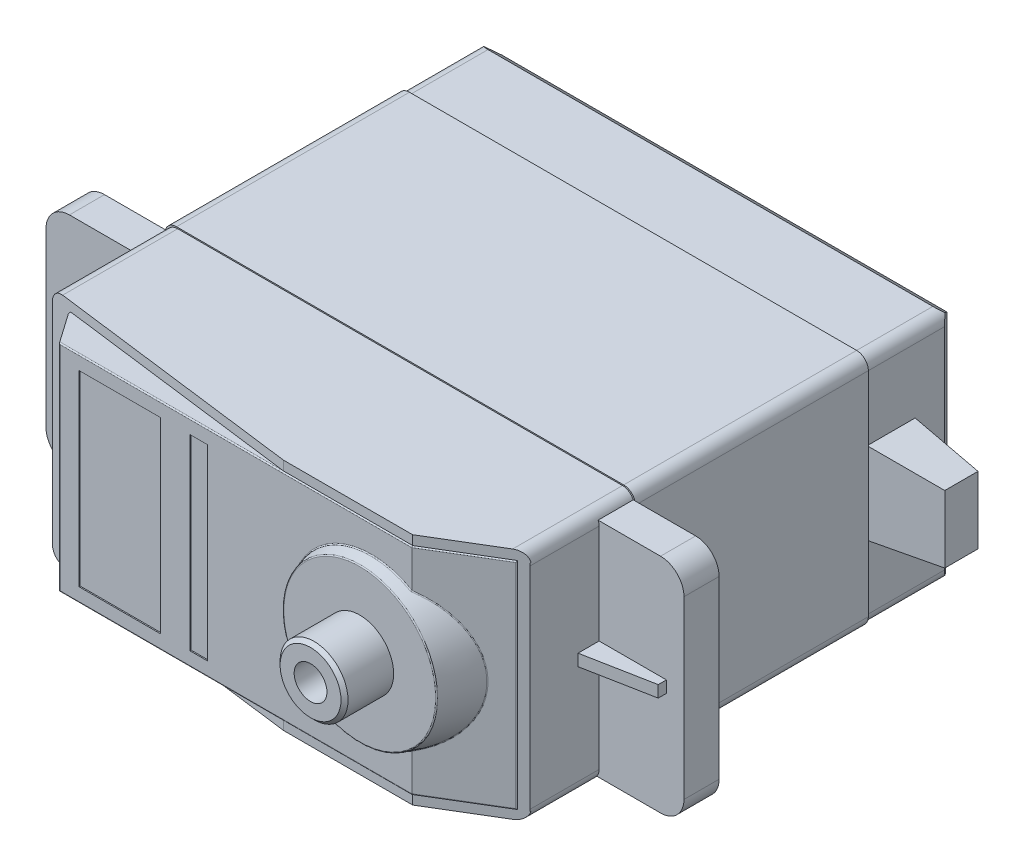
SolidWorks part; units mm, degrees
ref_plane "正面" through (0, 0, 0) normal (0, 0, 1) x (1, 0, 0)
ref_plane "平面" through (0, 0, 0) normal (0, 1, 0) x (1, 0, 0)
ref_plane "右側面" through (0, 0, 0) normal (1, 0, 0) x (0, 0, -1)
sketch "ｽｹｯﾁ1" plane through (0, 0, 0) normal (0, 0, 1) x (1, 0, 0)
  line L1 (20, -10) -> (-20, -10)
  line L2 (20, -10) -> (20, 10)
  line L3 (20, 10) -> (-20, 10)
  line L4 (-20, -10) -> (-20, 10)
  line L5 (20, -10) -> (-20, 10) construction
  line L6 (20, 10) -> (-20, -10) construction
  point P0 (0, 0)
  dimension "D1" = 40
  dimension "D2" = 20
extrude "ﾎﾞｽ - 押し出し1" add sketch "ｽｹｯﾁ1" along normal blind 40.4
chamfer "面取り1" distance 1 angle 50 4 edges at (0, -10, 0) (20, 0, 0) (0, 10, 0) (-20, 0, 0) first distance on face at (0, 0, 0)
ref_plane "平面1" through (0, 0, 27.7) normal (0, 0, -1) x (-1, 0, 0)
sketch "ｽｹｯﾁ3" plane through (0, 0, 27.7) normal (0, 0, -1) x (-1, 0, 0)
  line L0 (-20, -10) -> (-20, 10) construction
  line L1 (-20, -9.6) -> (-27.25, -9.6)
  line L2 (-20, -9.6) -> (-20, 9.4)
  line L3 (-20, 9.4) -> (-27.25, 9.4)
  line L4 (-27.25, -9.6) -> (-27.25, 9.4)
  line L5 (20, 10) -> (20, -10) construction
  line L6 (20, -9.3258) -> (27.25, -9.3258)
  line L7 (20, -9.3258) -> (20, 9.4)
  line L8 (20, 9.4) -> (27.25, 9.4)
  line L9 (27.25, -9.3258) -> (27.25, 9.4)
  line L10 (-20, 10) -> (20, 10) construction
  dimension "D1" = 0.6
  dimension "D2" = 19
  dimension "D3" = 54.5
extrude "ﾎﾞｽ - 押し出し2" add sketch "ｽｹｯﾁ3" against normal blind 3
sketch "ｽｹｯﾁ4" plane through (0, 0, 0) normal (0, 1, 0) x (1, 0, 0)
  line L0 (-25.75, -30.7) -> (-25.75, -31.4)
  line L1 (-27.25, -30.7) -> (-20, -30.7) construction
  line L2 (-25.75, -31.4) -> (-20, -32.5)
  line L3 (-20, -40.4) -> (-20, -1.1918) construction
  line L4 (-20, -32.5) -> (-20, -30.7)
  line L5 (-20, -30.7) -> (-25.75, -30.7)
  line L6 (-27.25, -30.7) -> (-27.25, -27.7) construction
  dimension "D1" = 1.8
  dimension "D2" = 0.7
  dimension "D3" = 1.5
extrude "ﾎﾞｽ - 押し出し3" add sketch "ｽｹｯﾁ4" along normal mid plane 1
mirror "ﾐﾗｰ1" about plane through (0, 0, 0) normal (1, 0, 0) of "ﾎﾞｽ - 押し出し3"
fillet "ﾌｨﾚｯﾄ1" radius 1 4 edges at (20, -10, 20.7959) (20, 10, 20.7959) (-20, 10, 20.7959) (-20, -10, 20.7959)
fillet "ﾌｨﾚｯﾄ2" radius 2 4 edges at (-27.25, 9.4, 29.2) (27.25, 9.4, 29.2) (27.25, -9.6, 29.2) (-27.25, -9.3258, 29.2)
sketch "ｽｹｯﾁ5" plane through (0, 0, 40.4) normal (0, 0, 1) x (1, 0, 0)
  line L0 (-27.25, -7.3258) -> (-27.25, 7.4) construction
  circle A0 centre (10.25, 0) radius 7.5
  dimension "D1" = 37.5
  dimension "D2" = 15
extrude "ﾎﾞｽ - 押し出し4" add sketch "ｽｹｯﾁ5" along normal blind 1
sketch "ｽｹｯﾁ11" plane through (0, -10, 0) normal (0, -1, 0) x (1, 0, 0)
  line L0 (13.7, 40.4) -> (20, 36.6)
  line L1 (-19, 40.4) -> (19, 40.4) construction
  line L2 (20, 40.4) -> (20, 30.7) construction
  line L3 (20, 36.6) -> (20, 41.6)
  line L5 (13.7, 40.4) -> (13.7, 41.6)
  line L7 (13.7, 41.6) -> (20, 41.6)
  line L9 (20, 40.4) -> (19, 40.4) construction
  dimension "D1" = 3.8
  dimension "D2" = 6.3
  dimension "D3" = 5
extrude "ｶｯﾄ - 押し出し2" cut sketch "ｽｹｯﾁ11" against normal through all
sketch "ｽｹｯﾁ13" plane through (0, 0, 41.4) normal (0, 0, 1) x (1, 0, 0)
  circle A0 centre (10.25, 0) radius 7.5
  arc A1 (13.7, 6.6594) -> (13.7, -6.6594) centre (10.25, 0) ccw construction
extrude "ﾎﾞｽ - 押し出し8" add sketch "ｽｹｯﾁ13" against normal blind 7.8
chamfer "面取り2" distance 3.5 angle 15 1 edges at (17.75, 0, 41.4) first distance on face at (17.75, 0, 41.4)
sketch "ｽｹｯﾁ6" plane through (0, -10, 0) normal (0, -1, 0) x (-1, 0, 0)
  line L0 (-3.4199, -40.4) -> (20, -37.4)
  line L1 (20, -30.7) -> (20, -40.4) construction
  line L2 (20, -37.4) -> (20, -40.4)
  line L3 (20, -40.4) -> (-3.4199, -40.4)
  dimension "D1" = 3
extrude "ｶｯﾄ - 押し出し1" cut sketch "ｽｹｯﾁ6" against normal through all
sketch "ｽｹｯﾁ7" plane through (0, 0, 0) normal (0, 0, -1) x (-1, 0, 0)
  line L0 (20, 9) -> (20, -9) construction
  line L1 (18.2, 9.2) -> (-6.8, 9.2)
  line L2 (18.2, 9.2) -> (18.2, -9.2)
  line L3 (18.2, -9.2) -> (-6.8, -9.2)
  line L4 (-6.8, 9.2) -> (-6.8, -9.2)
  line L5 (-19, 10) -> (19, 10) construction
  line L6 (19, -10) -> (-19, -10) construction
  dimension "D1" = 1.8
  dimension "D2" = 0.8
  dimension "D3" = 0.8
  dimension "D4" = 25
extrude "ﾎﾞｽ - 押し出し5" add sketch "ｽｹｯﾁ7" against normal up to surface (40.4 mm away) from offset 1 up to face at (8.1331, -7.2181, 40.4) offset against normal yes
chamfer "面取り3" distance 1.8 angle 55 1 edges at (-18.2, 0, 40.4) first distance on face at (2.1799, 0, 40.4)
sketch "ｽｹｯﾁ9" plane through (0, 0, 27.7) normal (0, 0, -1) x (-1, 0, 0)
  line L0 (-20, -9) -> (-20, 9) construction
  line L1 (20.1, -10.1) -> (-20.1, -10.1)
  line L2 (20.1, -10.1) -> (20.1, 10.1)
  line L3 (20.1, 10.1) -> (-20.1, 10.1)
  line L4 (-20.1, -10.1) -> (-20.1, 10.1)
  line L5 (20.1, -10.1) -> (-20.1, 10.1) construction
  line L6 (20.1, 10.1) -> (-20.1, -10.1) construction
  line L7 (-19, 10) -> (19, 10) construction
  point P0 (0, 0)
  dimension "D1" = 0.1
  dimension "D2" = 0.1
extrude "ﾎﾞｽ - 押し出し6" add sketch "ｽｹｯﾁ9" along normal offset from surface (19.9 mm away) 7.8 up to face at (0, 0, 0)
fillet "ﾌｨﾚｯﾄ3" radius 1 4 edges at (-20.1, -10.1, 17.75) (-20.1, 10.1, 17.75) (20.1, -10.1, 17.75) (20.1, 10.1, 17.75)
sketch "ｽｹｯﾁ14" plane through (0, 0, 40.4) normal (0, 0, 1) x (1, 0, 0)
  line L0 (3.4199, -9.2) -> (-16.4, -9.2) construction
  line L1 (2.3628, -9.2) -> (14.4548, -9.2)
  line L2 (2.3628, -9.2) -> (2.3628, -10)
  line L3 (2.3628, -10) -> (14.4548, -10)
  line L4 (14.4548, -9.2) -> (14.4548, -10)
  line L5 (3.4199, -10) -> (13.7, -10) construction
extrude "ｶｯﾄ - 押し出し3" cut sketch "ｽｹｯﾁ14" against normal blind 0.1
sketch "ｽｹｯﾁ15" plane through (21.5223, 0, 35.6818) normal (0.5165, 0, 0.8563) x (0.8563, 0, -0.5165)
  line L0 (-8.9415, -10) -> (-2.9457, -10) construction
  line L1 (-9.1351, -9.2) -> (-1.0779, -9.2)
  line L2 (-9.1351, -9.2) -> (-9.1351, -10)
  line L3 (-9.1351, -10) -> (-1.0779, -10)
  line L4 (-1.0779, -9.2) -> (-1.0779, -10)
extrude "ｶｯﾄ - 押し出し4" cut sketch "ｽｹｯﾁ15" against normal blind 0.1
sketch "ｽｹｯﾁ16" plane through (21.5223, 0, 35.6818) normal (0.5165, 0, 0.8563) x (0.8563, 0, -0.5165)
  line L0 (-1.7778, 9) -> (-1.7778, -9) construction
  line L1 (-2.5778, -10.1) -> (-1.7778, -10.1)
  line L2 (-2.5778, -10.1) -> (-2.5778, 10)
  line L3 (-2.5778, 10) -> (-1.7778, 10)
  line L4 (-1.7778, -10.1) -> (-1.7778, 10)
  line L5 (-9.1073, -10) -> (-9.1073, -9.2) construction
  line L6 (2.0483, -10.1) -> (-30.662, -10.1) construction
  line L7 (-30.5764, 10) -> (1.9627, 10) construction
extrude "ｶｯﾄ - 押し出し5" cut sketch "ｽｹｯﾁ16" against normal blind 0.1
mirror "ﾐﾗｰ2" about plane through (0, 0, 0) normal (0, 1, 0) of "ｶｯﾄ - 押し出し4", "ｶｯﾄ - 押し出し3"
fillet "ﾌｨﾚｯﾄ4" radius 0.1 11 edges at (16.5075, -9.2, 38.7066) (17.7317, 0, 37.9682) (16.5075, 9.2, 38.7066) (19.315, 0, 37.0132) (3.4199, 0, 40.4) (13.7, -7.5474, 40.4) (-1.35, -9.2, 40.4) (-16.4, 0, 40.4) (-1.35, 9.2, 40.4) (13.7, 7.5474, 40.4) (16.8122, 0, 41.4)
sketch "ｽｹｯﾁ17" plane through (20, 0, 0) normal (1, 0, 0) x (0, 0, -1)
  line L0 (-7.8, -9) -> (-7.8, 9) construction
  line L1 (-3.7, -3.5) -> (-7.8, -3.5)
  line L2 (-3.7, -3.5) -> (-3.7, 3.5)
  line L3 (-3.7, 3.5) -> (-7.8, 3.5)
  line L4 (-7.8, -3.5) -> (-7.8, 3.5)
  line L5 (-3.7, -3.5) -> (-7.8, 3.5) construction
  line L6 (-3.7, 3.5) -> (-7.8, -3.5) construction
  line L7 (0, 9) -> (0, -9) construction
  point P0 (-5.75, 0)
  dimension "D1" = 7
  dimension "D2" = 3.7
extrude "ﾎﾞｽ - 押し出し9" add sketch "ｽｹｯﾁ17" along normal blind 6 draft 6
sketch "ｽｹｯﾁ18" plane through (0, 0, 41.4) normal (0, 0, 1) x (1, 0, 0)
  circle A0 centre (10.25, 0) radius 2.9
  circle A1 centre (10.25, 0) radius 1.4
  dimension "D1" = 5.8
  dimension "D2" = 2.8
extrude "ﾎﾞｽ - 押し出し10" add sketch "ｽｹｯﾁ18" along normal blind 4.2
chamfer "面取り4" distance 0.3 angle 45 1 edges at (13.15, 0, 45.6)
sketch "ｽｹｯﾁ19" plane through (0, 0, 40.4) normal (0, 0, 1) x (1, 0, 0)
  line L0 (-27.25, -7.3258) -> (-27.25, 7.4) construction
  line L1 (-14.75, 8) -> (-7.75, 8)
  line L2 (-14.75, 8) -> (-14.75, -8)
  line L3 (-14.75, -8) -> (-7.75, -8)
  line L4 (-3.75, 8) -> (-3.75, -8)
  line L5 (-5.25, 8) -> (-3.75, 8)
  line L7 (-5.25, 8) -> (-5.25, -8)
  line L9 (-7.75, 8) -> (-7.75, -8)
  line L10 (-5.25, -8) -> (-3.75, -8)
  point P6 (-3.75, 0)
  dimension "D1" = 12.5
  dimension "D2" = 16
  dimension "D3" = 11
  dimension "D4" = 1.5
  dimension "D5" = 2.5
extrude "ｶｯﾄ - 押し出し6" cut sketch "ｽｹｯﾁ19" against normal blind 0.1
